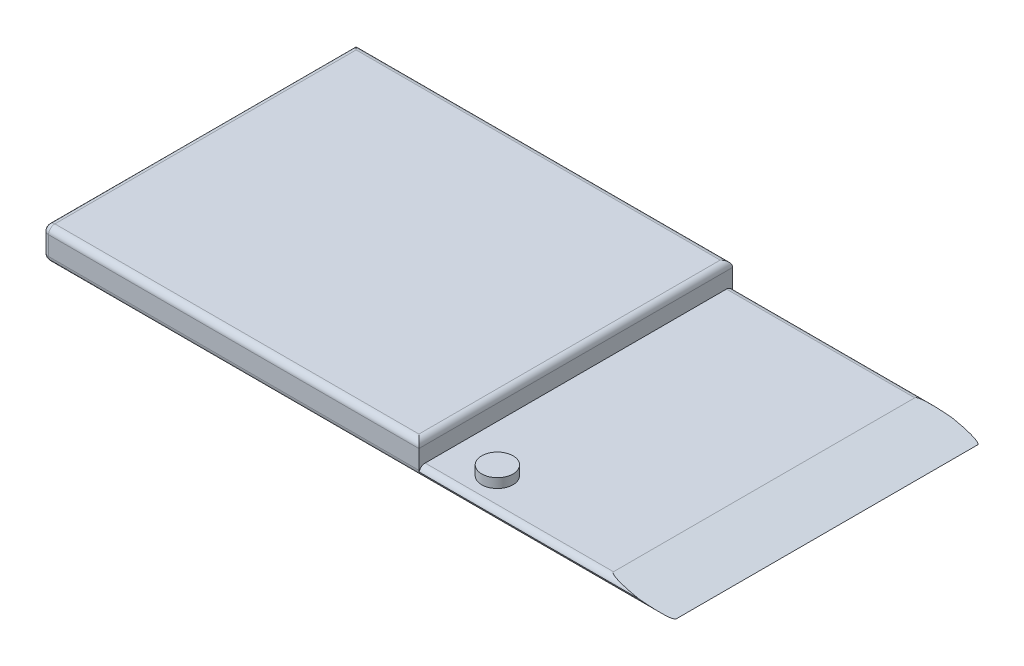
SolidWorks part; units mm, degrees
ref_plane "Front Plane" through (0, 0, 0) normal (0, 0, 1) x (1, 0, 0)
ref_plane "Top Plane" through (0, 0, 0) normal (0, 1, 0) x (1, 0, 0)
ref_plane "Right Plane" through (0, 0, 0) normal (1, 0, 0) x (0, 0, -1)
sketch "Sketch1" plane through (0, 0, 0) normal (0, 1, 0) x (1, 0, 0)
  line L1 (-127, 63.5) -> (127, 63.5)
  line L2 (-127, 63.5) -> (-127, -63.5)
  line L3 (-127, -63.5) -> (127, -63.5)
  line L4 (127, 63.5) -> (127, -63.5)
  line L5 (-127, 63.5) -> (127, -63.5) construction
  line L6 (-127, -63.5) -> (127, 63.5) construction
  point P0 (0, 0)
  dimension "D1" = 254
  dimension "D2" = 127
extrude "Boss-Extrude1" add sketch "Sketch1" along normal blind 12.7
sketch "Sketch2" plane through (0, 0, 63.5) normal (0, 0, 1) x (1, 0, 0)
  line L0 (25.4, 12.7) -> (25.4, 3.81)
  line L1 (-127, 12.7) -> (127, 12.7) construction
  line L2 (25.4, 3.81) -> (101.6, 3.81)
  line L3 (101.6, 3.81) -> (127, 0)
  line L8 (-127, 0) -> (127, 0)
  line L9 (127, 0) -> (127, 12.7)
  line L10 (127, 12.7) -> (-127, 12.7)
  line L11 (-127, 12.7) -> (-127, 0)
  line L12 (-127, 0) -> (127, 0)
  line L14 (25.4, 12.7) -> (-127, 12.7)
  line L15 (-127, 12.7) -> (-127, 0)
  point P9 (0, 0)
  dimension "D1" = 0
extrude "Cut-Extrude2" cut sketch "Sketch2" against normal through all flip side to cut
fillet "Fillet1" radius 2.54 4 edges at (25.4, 12.7, 0) (-50.8, 12.7, -63.5) (-127, 12.7, 0) (-50.8, 12.7, 63.5)
fillet "Fillet4" radius 2.54 3 edges at (63.5, 3.81, -63.5) (63.5, 3.81, 63.5) (0, 0, 63.5)
fillet "Fillet5" radius 2.54 5 edges at (-126.2561, 11.9561, 62.7561) (-127, 6.35, 63.5) (-127, 0.7439, 62.7561) (-127, 0, -1.27) (0, 0, -63.5)
sketch "Sketch3" plane through (0, 3.81, 0) normal (0, 1, 0) x (1, 0, 0)
  circle A0 centre (44.45, -50.8) radius 6.35
  point P2 (0, 0)
  point P3 (0, 0)
extrude "Boss-Extrude2" add sketch "Sketch3" along normal blind 3.81
